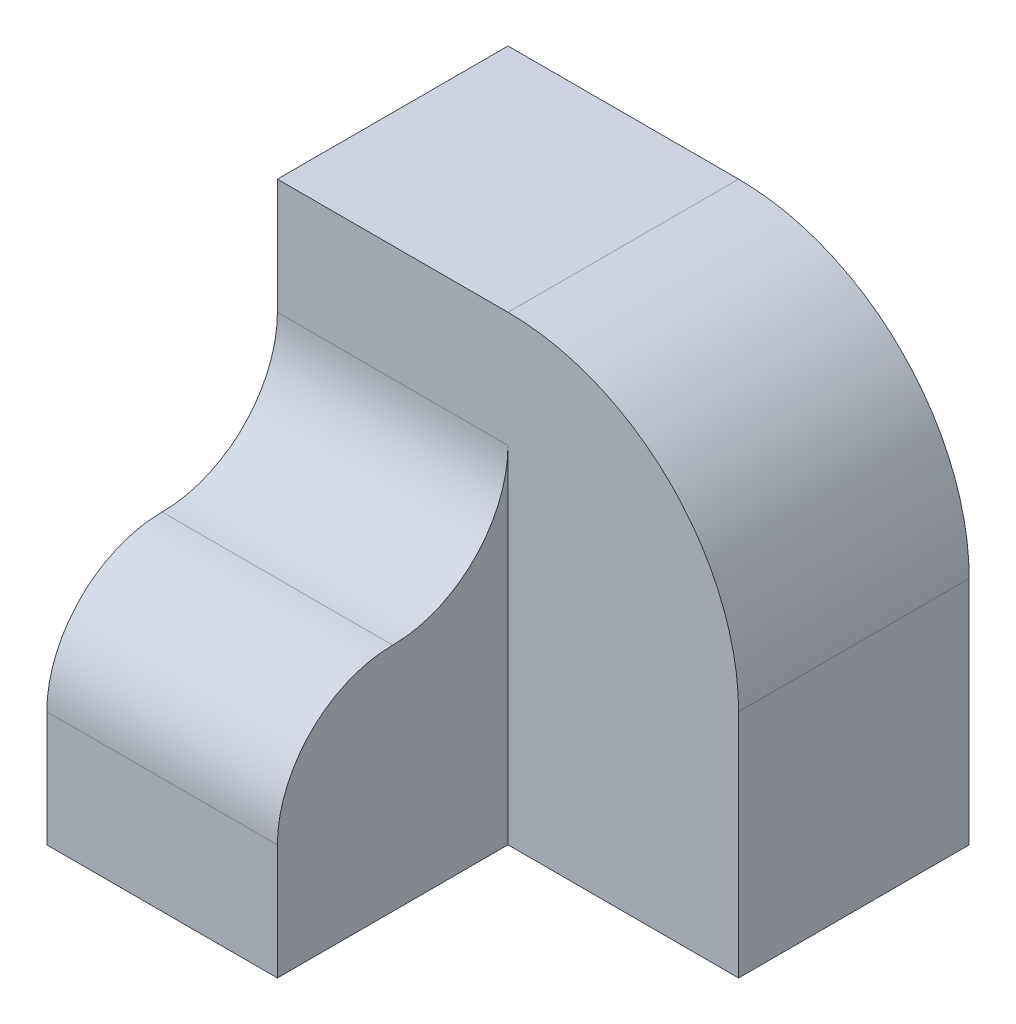
SolidWorks part; units mm, degrees
ref_plane "Płaszczyzna przednia" through (0, 0, 0) normal (0, 0, 1) x (1, 0, 0)
ref_plane "Płaszczyzna górna" through (0, 0, 0) normal (0, 1, 0) x (1, 0, 0)
ref_plane "Płaszczyzna prawa" through (0, 0, 0) normal (1, 0, 0) x (0, 0, -1)
sketch "Szkic1" plane through (0, 0, 0) normal (0, 0, 1) x (1, 0, 0)
  line L0 (0, 0) -> (40, 0)
  line L1 (40, 0) -> (40, 20)
  line L2 (20, 40) -> (0, 40)
  line L3 (0, 40) -> (0, 0)
  arc A0 (40, 20) -> (20, 40) centre (20, 20) ccw
  dimension "D1" = 20
  dimension "D2" = 40
  dimension "D3" = 40
extrude "Dodanie-wyciągnięcie1" add sketch "Szkic1" along normal blind 20
sketch "Szkic2" plane through (0, 0, 20) normal (0, 0, 1) x (1, 0, 0)
  line L0 (0, 0) -> (20, 0)
  line L1 (0, 0) -> (40, 0) construction
  line L2 (20, 0) -> (20, 40)
  line L3 (20, 40) -> (0, 40)
  line L4 (0, -22) -> (0, 22) construction
  line L5 (20, 40) -> (0, 40) construction
  line L6 (0, 40) -> (0, 0)
extrude "Dodanie-wyciągnięcie2" add sketch "Szkic2" along normal blind 20
sketch "Szkic3" plane through (20, 0, 0) normal (1, 0, 0) x (0, 0, -1)
  line L0 (-40, 0) -> (-40, 10)
  line L1 (-40, 0) -> (-40, 40) construction
  line L2 (-30, 20) -> (-20, 20)
  line L3 (-20, 0) -> (-20, 40) construction
  line L4 (-20, 20) -> (-20, 40)
  line L6 (-40, 40) -> (-20, 40)
  line L7 (-40, 40) -> (-40, 20)
  line L8 (-40, 20) -> (-20, 20)
  line L9 (-20, 40) -> (-20, 20)
  arc A0 (-40, 10) -> (-30, 20) centre (-30, 10) cw
  point P12 (-40, 20)
  line M7 (-20, 0) -> (-20, 40)
  line M8 (-20, 40) -> (-40, 40)
  line M9 (-40, 40) -> (-40, 0)
  dimension "D1" = 10
extrude "Wytnij-wyciągnięcie1" cut sketch "Szkic3" against normal blind 20 contours L8 L2 M9 M7 M8 region at (20, 30, 30)
fillet "Zaokrąglenie1" radius 10 1 edges at (10, 20, 20)
fillet "Zaokrąglenie2" radius 10 1 edges at (10, 20, 40)
